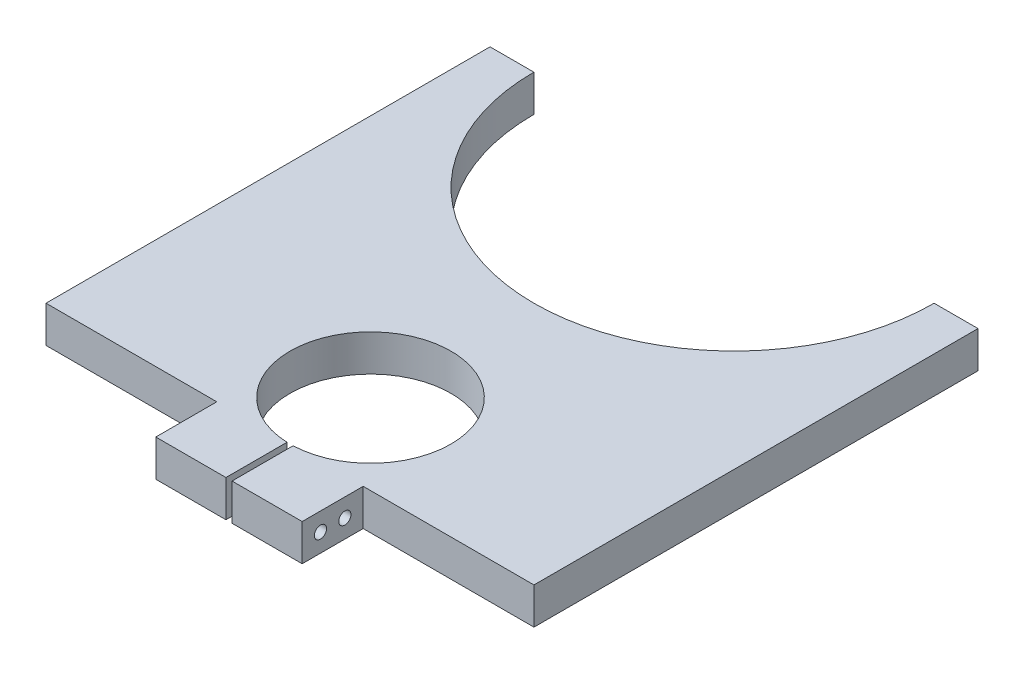
SolidWorks part; units mm, degrees
ref_plane "Front Plane" through (0, 0, 0) normal (0, 0, 1) x (1, 0, 0)
ref_plane "Top Plane" through (0, 0, 0) normal (0, 1, 0) x (1, 0, 0)
ref_plane "Right Plane" through (0, 0, 0) normal (1, 0, 0) x (0, 0, -1)
sketch "Sketch1" plane through (0, 0, 0) normal (0, 1, 0) x (1, 0, 0)
  line L0 (0, 0) -> (0, -131.445)
  line L1 (0, -131.445) -> (127, -131.445)
  line L2 (127, -131.445) -> (127, 0)
  line L3 (127, 0) -> (0, 0)
  dimension "D1" = 127
  dimension "D2" = 131.445
extrude "Boss-Extrude1" add sketch "Sketch1" along normal blind 9.525
sketch "Sketch2" plane through (0, 9.525, 0) normal (0, 1, 0) x (1, 0, 0)
  line L0 (0, -131.445) -> (44.45, -131.445)
  line L1 (0, -131.445) -> (127, -131.445) construction
  line L2 (127, -131.445) -> (82.55, -131.445)
  line L3 (44.45, -131.445) -> (44.45, -115.57)
  line L4 (44.45, -115.57) -> (0, -115.57)
  line L5 (0, 0) -> (0, -131.445) construction
  line L6 (0, -115.57) -> (0, -131.445)
  line L7 (82.55, -131.445) -> (82.55, -115.57)
  line L8 (82.55, -115.57) -> (127, -115.57)
  line L9 (127, -131.445) -> (127, 0) construction
  line L10 (127, -115.57) -> (127, -131.445)
  dimension "D1" = 44.45
  dimension "D2" = 44.45
  dimension "D3" = 15.875
extrude "Cut-Extrude1" cut sketch "Sketch2" against normal through all
sketch "Sketch3" plane through (0, 9.525, 0) normal (0, 1, 0) x (1, 0, 0)
  line L0 (63.5, -131.445) -> (64.2938, -131.445)
  line L1 (44.45, -131.445) -> (82.55, -131.445) construction
  line L2 (63.5, -131.445) -> (62.7063, -131.445)
  line L3 (62.7063, -131.445) -> (62.7063, -115.57)
  line L5 (64.2938, -115.57) -> (64.2938, -131.445)
  line L7 (64.2938, -115.57) -> (64.2938, -115.555)
  line L8 (62.7063, -115.57) -> (62.7063, -115.555)
  arc A0 (64.2938, -115.555) -> (62.7063, -115.555) centre (63.5, -94.615) ccw
  dimension "D1" = 0.7937
  dimension "D2" = 0.7937
extrude "Cut-Extrude2" cut sketch "Sketch3" against normal through all
sketch "Sketch5" plane through (0, 9.525, 0) normal (0, 1, 0) x (1, 0, 0)
  line L0 (127, 0) -> (0, 0)
  circle A0 centre (63.5, 0) radius 52.0852
  dimension "D1" = 104.1705
extrude "Cut-Extrude3" cut sketch "Sketch5" against normal through all contours L0 A0 region at (63.5, 9.525, 22.1057)
sketch "Sketch6" plane through (44.45, 0, 0) normal (-1, 0, 0) x (0, 0, 1)
  line L0 (131.445, 0) -> (131.445, 9.525) construction
  circle A0 centre (120.3325, 4.7625) radius 1.5875
  circle A1 centre (126.6825, 4.7625) radius 1.5875
  dimension "D1" = 3.175
  dimension "D2" = 3.175
  dimension "D3" = 4.7625
  dimension "D4" = 11.1125
extrude "Cut-Extrude4" cut sketch "Sketch6" against normal through all
